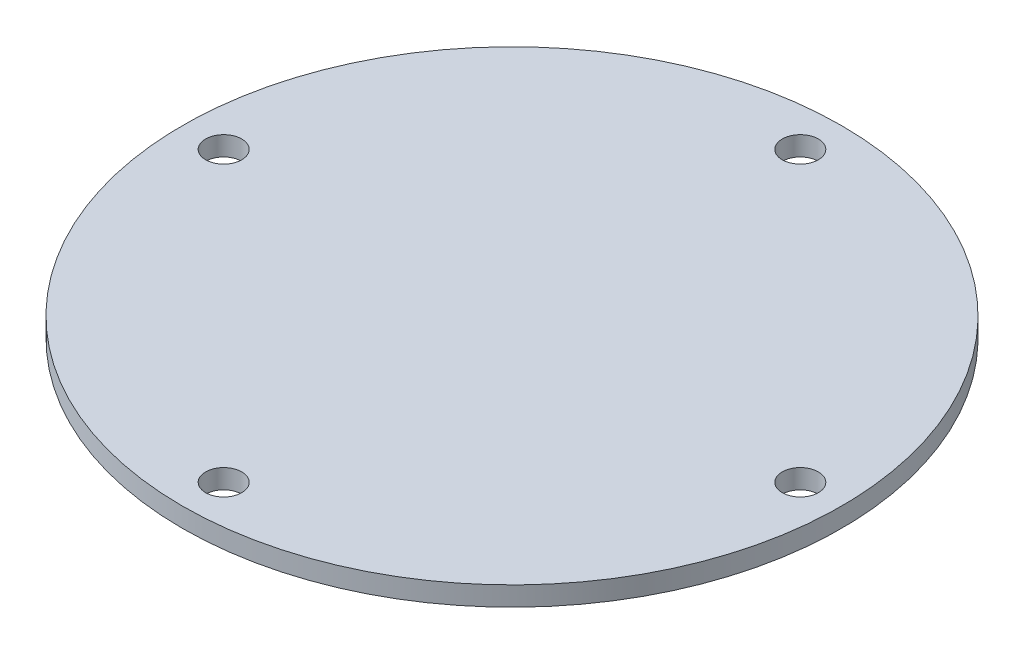
SolidWorks part; units mm, degrees
ref_plane "Front Plane" through (0, 0, 0) normal (0, 0, 1) x (1, 0, 0)
ref_plane "Top Plane" through (0, 0, 0) normal (0, 1, 0) x (1, 0, 0)
ref_plane "Right Plane" through (0, 0, 0) normal (1, 0, 0) x (0, 0, -1)
sketch "Sketch1" plane through (0, 0, 0) normal (0, 1, 0) x (1, 0, 0)
  circle A0 centre (0, 0) radius 63.9
  dimension "PCBdiam" = 127.8
extrude "Boss-Extrude1" add sketch "Sketch1" along normal blind 3.75
hole_wizard "M6 Clearance Hole1" positions "Sketch2" profile "Sketch4" hole size "M6" standard "ANSI Metric" end condition through all
sketch "Sketch2" plane through (0, 3.75, 0) normal (0, 1, 0) x (1, 0, 0)
  line L0 (0, 0) -> (0, 29.5662) construction
  circle A0 centre (0, 0) radius 63.9 construction
  point P7 (-55.9, 0)
  dimension "holeRadius" = 55.9
sketch "Sketch4" plane through (-55.9, 3.75, 0) normal (1, 0, 0) x (0, 0, 1)
  line L0 (0, 0) -> (0, 3.75)
  line L1 (0, 3.75) -> (3.5, 3.75)
  line L2 (3.5, 3.75) -> (3.5, 0)
  line L5 (3.5, 0) -> (0, 0)
  line L11 (0, -6.35) -> (0, 107.95) construction
  dimension "Thru Hole Dia." = 7
  dimension "Thru Hole Depth" = 3.75
pattern_circular "CirPattern1" count 4 over 360 about axis through (0, 3.75, 0) along (0, -1, 0) of "M6 Clearance Hole1"
sketch "Sketch5" plane through (0, 3.75, 0) normal (0, 1, 0) x (1, 0, 0)
  arc A0 (-31.9347, 32.9281) -> (-41.7327, 32.9281) centre (-36.8337, 33.9281) ccw construction
  arc A1 (-31.9347, 32.9281) -> (-41.7327, 32.9281) centre (-36.8337, 33.9281) ccw construction
  circle A2 centre (-36.8337, 33.9281) radius 7
  dimension "D1" = 14
extrude "Cut-Extrude1" [suppressed] cut sketch "Sketch5" against normal through all contours A2
